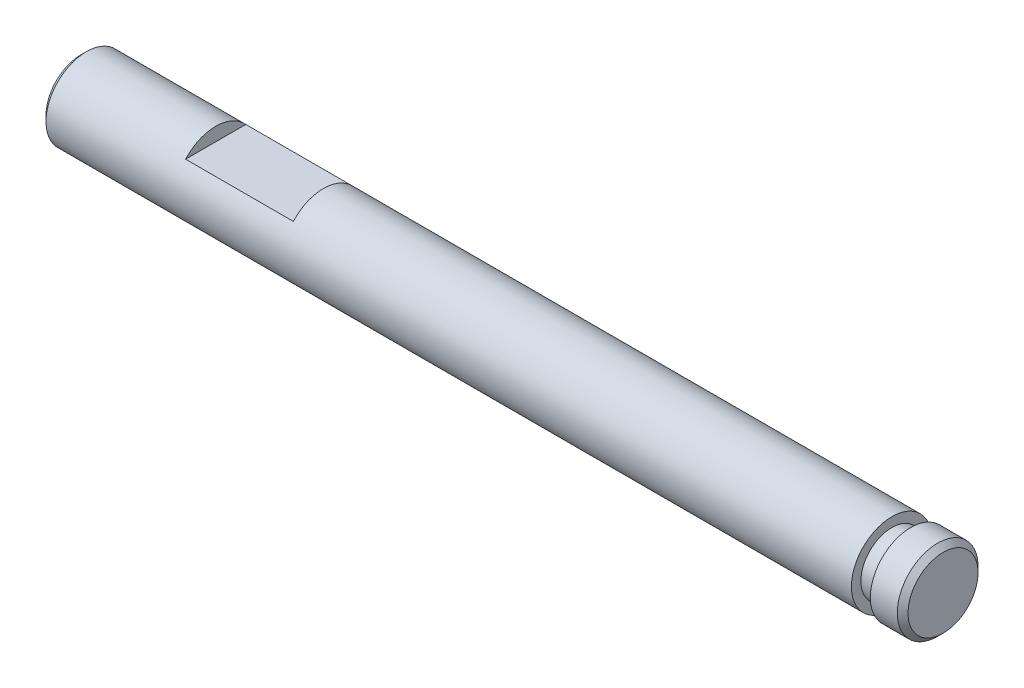
SolidWorks part; units mm, degrees
ref_plane "Plan de face" through (0, 0, 0) normal (0, 0, 1) x (1, 0, 0)
ref_plane "Plan de dessus" through (0, 0, 0) normal (0, 1, 0) x (1, 0, 0)
ref_plane "Plan de droite" through (0, 0, 0) normal (1, 0, 0) x (0, 0, -1)
sketch "Esquisse1" plane through (0, 0, 0) normal (0, 0, 1) x (1, 0, 0)
  line L0 (0, 0) -> (32, 0) construction
  line L1 (32, 0) -> (32, 1.5)
  line L2 (0, 0) -> (32, 0)
  line L3 (32, 1.5) -> (30.8, 1.5)
  line L4 (30.8, 1.5) -> (30.8, 1.15)
  line L5 (30.8, 1.15) -> (30.1, 1.15)
  line L6 (30.1, 1.15) -> (30.1, 1.5)
  line L7 (30.1, 1.5) -> (0, 1.5)
  line L8 (0, 1.5) -> (0, 0)
  dimension "D1" = 32
  dimension "D2" = 3
  dimension "D3" = 2.3
  dimension "D4" = 0.7
  dimension "D5" = 1.2
revolve "Révolution1" add sketch "Esquisse1" angle 360 about L0
chamfer "Chanfrein1" distance 0.2 angle 45 2 edges at (32, 0, 1.5) (0, 0, 1.5)
sketch "Esquisse2" plane through (0, 0, 0) normal (0, 0, 1) x (1, 0, 0)
  line L0 (7, 2.9886) -> (7, 1) construction
  line L1 (5, 2.9886) -> (9, 2.9886)
  line L2 (5, 2.9886) -> (5, 1)
  line L3 (5, 1) -> (9, 1)
  line L4 (9, 2.9886) -> (9, 1)
  line L5 (32, -1.3) -> (32, 1.3) construction
  line L6 (30.1, 1.5) -> (0.2, 1.5) construction
  dimension "D1" = 25
  dimension "D2" = 4
  dimension "D3" = 0.5
extrude "Extrusion1" cut sketch "Esquisse2" against normal blind 10 and the other way blind 10
